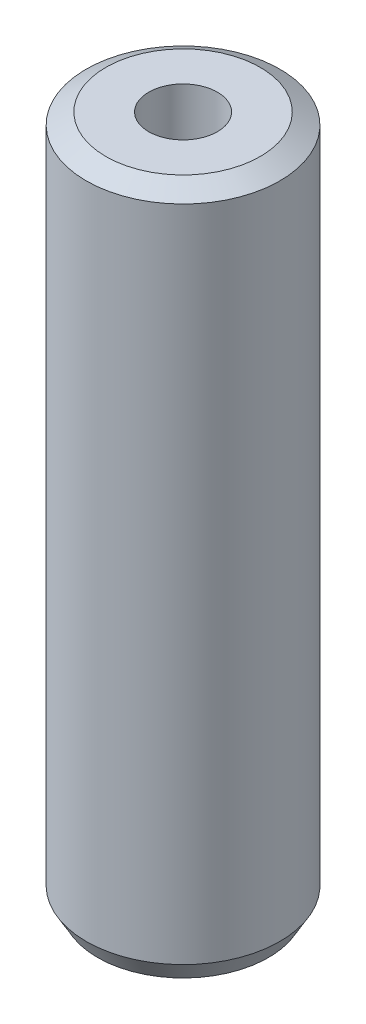
SolidWorks part; units mm, degrees
ref_plane "Front Plane" through (0, 0, 0) normal (0, 0, 1) x (1, 0, 0)
ref_plane "Top Plane" through (0, 0, 0) normal (0, 1, 0) x (1, 0, 0)
ref_plane "Right Plane" through (0, 0, 0) normal (1, 0, 0) x (0, 0, -1)
sketch "Sketch1" plane through (0, 0, 0) normal (0, 1, 0) x (1, 0, 0)
  circle A0 centre (0, 0) radius 5
  dimension "SHAFT_OD" = 10
extrude "Boss-Extrude1" add sketch "Sketch1" along normal blind 35.6103
sketch "Sketch2" plane through (0, 0, 0) normal (0, 1, 0) x (1, 0, 0)
  circle A0 centre (0, 0) radius 1.7723
  dimension "BORE_D" = 3.5446
extrude "Cut-Extrude1" cut sketch "Sketch2" along normal through all
chamfer "Chamfer1" distance 0.5839 angle 60 2 edges at (0, 35.6103, 5) (0, 0, 5) first distance on face at (0, 35.6103, 5) first distance on face at (0, 0, 1.7723)
